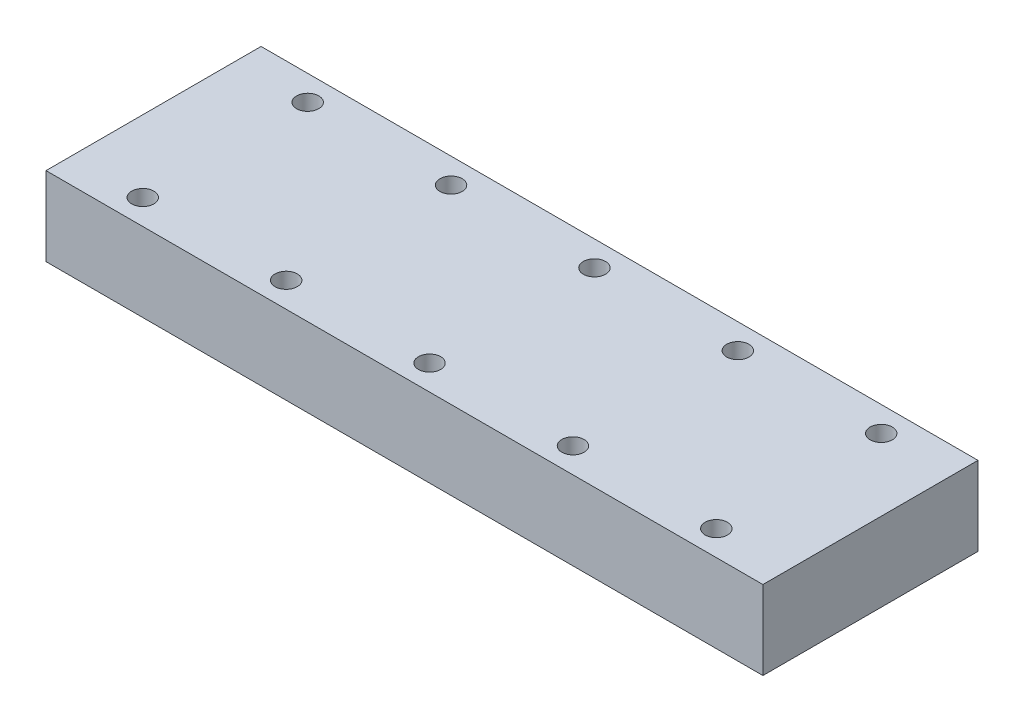
SolidWorks part; units mm, degrees
ref_plane "Front Plane" through (0, 0, 0) normal (0, 0, 1) x (1, 0, 0)
ref_plane "Top Plane" through (0, 0, 0) normal (0, 1, 0) x (1, 0, 0)
ref_plane "Right Plane" through (0, 0, 0) normal (1, 0, 0) x (0, 0, -1)
sketch "Sketch1" plane through (0, 0, 0) normal (0, 1, 0) x (1, 0, 0)
  line L0 (-55, 0) -> (-55, 30)
  line L1 (-55, 30) -> (45, 30)
  line L2 (45, 30) -> (45, 0)
  line L3 (45, 0) -> (-55, 0)
  dimension "D1" = 100
  dimension "D2" = 30
  dimension "D3" = 0
  dimension "D4" = 55
extrude "Boss-Extrude1" add sketch "Sketch1" along normal blind 11
sketch "Sketch4" plane through (0, 0, 0) normal (0, 1, 0) x (1, 0, 0)
  line L0 (-35, 6) -> (-50, 6)
  line L1 (-50, 6) -> (-50, 24)
  line L2 (-50, 24) -> (-20, 24)
  line L3 (-20, 24) -> (-20, 6)
  line L4 (-20, 6) -> (-35, 6)
  line L5 (-55, 30) -> (-55, 0) construction
  line L9 (45, 30) -> (-55, 30) construction
  line L10 (-55, 0) -> (45, 0) construction
  dimension "D1" = 18
  dimension "D2" = 6
  dimension "D3" = 5
  dimension "D4" = 30
  dimension "D5" = 6
extrude "Cut-Extrude1" cut sketch "Sketch4" against normal blind 8 and the other way blind 10.11
sketch "Sketch3" plane through (0, 0, 0) normal (0, 1, 0) x (1, 0, 0)
  line L0 (45, 15) -> (-55, 15) construction
  line L1 (45, 0) -> (45, 30) construction
  line L2 (-55, 30) -> (-55, 0) construction
  line L3 (40, 15) -> (40, 8.41)
  line L4 (40, 8.41) -> (-40, 6.89)
  line L5 (-40, 6.89) -> (-40, 15)
  line L6 (-40, 15) -> (40, 15)
  line L7 (-20, 6) -> (-20, 24) construction
  dimension "D1" = 6.59
  dimension "D2" = 8.11
  dimension "D3" = 80
  dimension "D4" = 20
revolve "Cut-Revolve1" cut sketch "Sketch3" angle 360 about L0
sketch "Sketch5" plane through (0, 0, 0) normal (0, 1, 0) x (1, 0, 0)
  line L0 (30, 8.22) -> (30, 10.72)
  line L1 (-20, 7.27) -> (40, 8.41) construction
  line L2 (30, 10.72) -> (17.5, 10.4825)
  line L3 (17.5, 10.4825) -> (17.5, 7.9825)
  line L4 (17.5, 7.9825) -> (30, 8.22)
  line L5 (40, 15) -> (-16.9672, 15) construction
  line L6 (40, 8.41) -> (40, 21.59) construction
  dimension "D1" = 2.5
  dimension "D2" = 2.5
  dimension "D3" = 12.5
  dimension "D4" = 10
revolve "Revolve1" add sketch "Sketch5" angle 45 about L5 other way angle 225
sketch "Sketch6" plane through (0, 0, 0) normal (0, 1, 0) x (1, 0, 0)
  line L0 (5, 7.745) -> (5, 10.245)
  line L1 (-20, 7.27) -> (17.5, 7.9825) construction
  line L2 (5, 10.245) -> (-7.5, 10.0075)
  line L3 (-7.5, 10.0075) -> (-7.5, 7.5075)
  line L4 (-7.5, 7.5075) -> (5, 7.745)
  line L5 (40, 15) -> (-17.599, 15) construction
  line L6 (40, 8.41) -> (40, 21.59) construction
  dimension "D1" = 2.5
  dimension "D2" = 2.5
  dimension "D3" = 12.5
  dimension "D4" = 12.5
revolve "Revolve2" add sketch "Sketch6" angle 45 about L5 other way angle 225
sketch "Sketch7" plane through (0, 0, 0) normal (0, 1, 0) x (1, 0, 0)
  line L0 (45, 0) -> (45, 30)
  line L1 (45, 30) -> (-55, 30)
  line L2 (-55, 30) -> (-55, 0)
  line L3 (-55, 0) -> (45, 0)
extrude "Cut-Extrude2" cut sketch "Sketch7" against normal blind 15
fillet "Fillet1" radius 1.2 20 edges at (17.5, 2.6855, -21.4833) (17.5, 1.7288, -19.1736) (5, 1.8197, -19.393) (5, 1.8197, -10.607) (17.5, 2.6855, -8.5167) (17.5, 1.7288, -10.8264) (5, 2.7764, -8.2973) (5, 2.7764, -21.7027) (30, 2.5946, -8.7361) (30, 2.5946, -21.2639) (23.75, 3.1104, -11.8896) (30, 1.6379, -11.0458) (30, 1.6379, -18.9542) (-7.5, 1.9105, -19.6125) (-7.5, 2.8673, -21.9222) (-7.5, 2.8673, -8.0778) (-7.5, 1.9105, -10.3875) (-1.25, 3.4463, -11.5537) (23.75, 3.1104, -18.1104) (-1.25, 3.4463, -18.4463)
ref_plane "Plane1" through (-55, 0, 0) normal (-1, 0, 0) x (0, 0, 1)
sketch "Sketch9" plane through (0, 0, 0) normal (0, 1, 0) x (1, 0, 0)
  line L0 (45, 0) -> (45, 30) construction
  line L3 (45, 30) -> (-55, 30) construction
  line L4 (45, 15) -> (-55.4355, 15) construction
  line L5 (-55, 0) -> (45, 0) construction
  circle A0 centre (35, 26.5) radius 1.55
  circle A1 centre (15, 26.5) radius 1.55
  circle A2 centre (-5, 26.5) radius 1.55
  circle A3 centre (-25, 26.5) radius 1.55
  circle A4 centre (-45, 26.5) radius 1.55
  circle A5 centre (35, 3.5) radius 1.55
  circle A6 centre (15, 3.5) radius 1.55
  circle A7 centre (-5, 3.5) radius 1.55
  circle A8 centre (-25, 3.5) radius 1.55
  circle A9 centre (-45, 3.5) radius 1.55
  dimension "D6" = 3.1
  dimension "D7" = 3.1
  dimension "D8" = 3.1
  dimension "D9" = 3.1
  dimension "D10" = 3.1
  dimension "D21" = 3.1
  dimension "D22" = 3.1
  dimension "D23" = 3.1
  dimension "D24" = 3.1
  dimension "D25" = 3.1
  dimension "D1" = 10
  dimension "D2" = 20
  dimension "D3" = 20
  dimension "D4" = 20
  dimension "D5" = 20
  dimension "D11" = 3.5
  dimension "D12" = 3.5
  dimension "D13" = 3.5
  dimension "D14" = 3.5
  dimension "D15" = 3.5
  dimension "D16" = 3.5
  dimension "D17" = 3.5
  dimension "D18" = 3.5
  dimension "D19" = 3.5
  dimension "D20" = 3.5
fillet "Fillet9" radius 1.2 7 edges at (-35, 10.11, -6) (-50, 5.055, -6) (-50, 5.055, -24) (-50, 10.11, -15) (-35, 10.11, -24) (-20, 7.73, -15) (-20, 10.11, -15)
fillet "Fillet10" radius 0.5 4 edges at (-20.3515, 9.7585, -6.3515) (-20.3515, 9.7585, -23.6485) (-20, 4.455, -6) (-20, 4.455, -24)
extrude "Cut-Extrude3" cut sketch "Sketch9" against normal blind 15 and the other way blind 20
